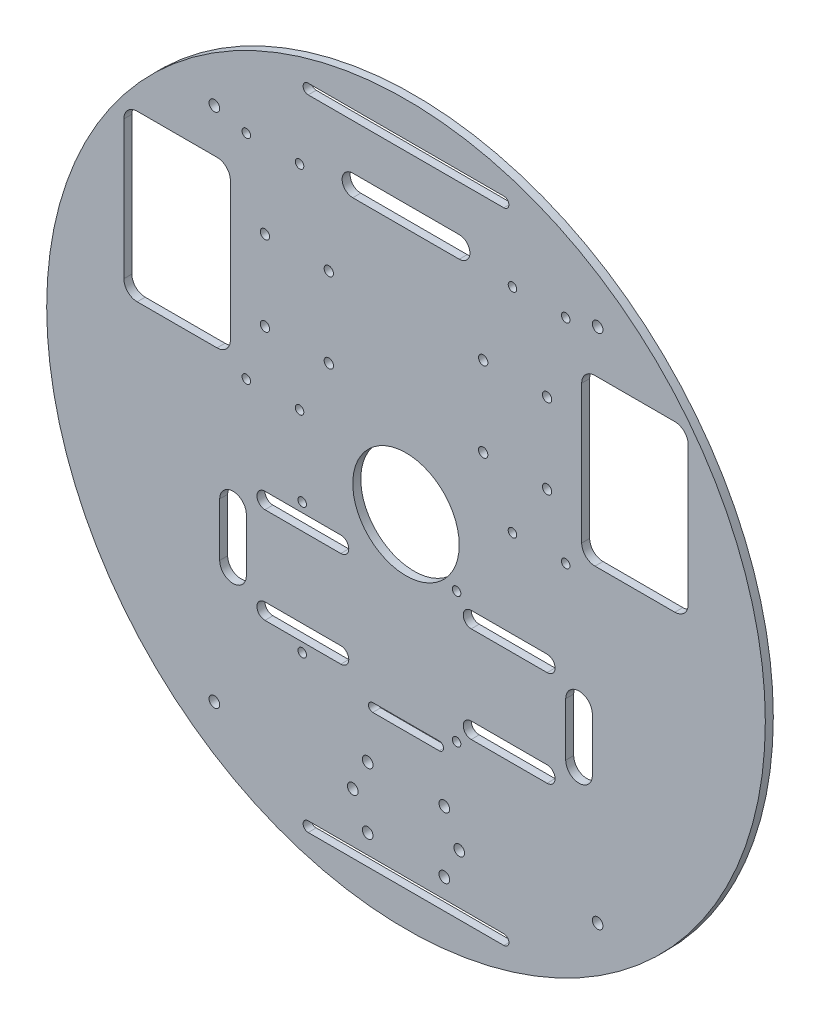
SolidWorks part; units mm, degrees
ref_plane "前视基准面" through (0, 0, 0) normal (0, 0, 1) x (1, 0, 0)
ref_plane "上视基准面" through (0, 0, 0) normal (0, 1, 0) x (1, 0, 0)
ref_plane "右视基准面" through (0, 0, 0) normal (1, 0, 0) x (0, 0, -1)
sketch "草图1" plane through (0, 0, 0) normal (0, 0, 1) x (1, 0, 0)
  line L0 (0, 135) -> (0, -135) construction
  line L1 (0, -99.3042) -> (86, 49.6521) construction
  line L2 (86, 49.6521) -> (-86, 49.6521) construction
  line L3 (-86, 49.6521) -> (0, -99.3042) construction
  line L4 (-106, 80.6521) -> (-66, 80.6521)
  line L5 (-106, 80.6521) -> (-106, 18.6521)
  line L6 (-106, 18.6521) -> (-66, 18.6521)
  line L7 (-66, 80.6521) -> (-66, 18.6521)
  line L8 (-106, 80.6521) -> (-66, 18.6521) construction
  line L9 (-106, 18.6521) -> (-66, 80.6521) construction
  line L10 (106, 80.6521) -> (66, 80.6521)
  line L11 (66, 80.6521) -> (66, 18.6521)
  line L12 (106, 80.6521) -> (66, 18.6521) construction
  line L13 (106, 18.6521) -> (66, 18.6521)
  line L14 (106, 18.6521) -> (66, 80.6521) construction
  line L15 (106, 80.6521) -> (106, 18.6521)
  line L17 (-14.4, -87.8042) -> (14.4, -87.8042) construction
  line L18 (-14.4, -87.8042) -> (-14.4, -110.8042) construction
  line L19 (-14.4, -110.8042) -> (14.4, -110.8042) construction
  line L20 (14.4, -87.8042) -> (14.4, -110.8042) construction
  line L21 (-14.4, -87.8042) -> (14.4, -110.8042) construction
  line L22 (-14.4, -110.8042) -> (14.4, -87.8042) construction
  line L29 (-53, 64.6521) -> (-29, 64.6521) construction
  line L30 (-53, 64.6521) -> (-53, 34.6521) construction
  line L31 (-53, 34.6521) -> (-29, 34.6521) construction
  line L32 (-29, 64.6521) -> (-29, 34.6521) construction
  line L33 (-53, 64.6521) -> (-29, 34.6521) construction
  line L34 (-53, 34.6521) -> (-29, 64.6521) construction
  circle A0 centre (0, 0) radius 135
  circle A1 centre (0, 0) radius 49.6521 construction
  circle A2 centre (-53, 64.6521) radius 1.75
  circle A3 centre (-29, 64.6521) radius 1.75
  circle A4 centre (-53, 34.6521) radius 1.75
  circle A5 centre (-29, 34.6521) radius 1.75
  circle A6 centre (53, 34.6521) radius 1.75
  circle A7 centre (29, 34.6521) radius 1.75
  circle A8 centre (29, 64.6521) radius 1.75
  circle A9 centre (53, 64.6521) radius 1.75
  circle A10 centre (20, -99.3042) radius 2
  circle A11 centre (14.4, -87.8042) radius 2
  circle A12 centre (14.4, -110.8042) radius 2
  circle A13 centre (-14.4, -87.8042) radius 2
  circle A14 centre (-14.4, -110.8042) radius 2
  circle A15 centre (-20, -99.3042) radius 2
  point P25 (0, 49.6521)
  point P26 (-41, 49.6521)
  point P30 (0, 49.6521)
  dimension "D1" = 270
  dimension "D9" = 3.5
  dimension "D10" = 3.5
  dimension "D11" = 3.5
  dimension "D12" = 3.5
  dimension "D14" = 20
  dimension "D2" = 40
  dimension "D3" = 62
  dimension "D4" = 41
  dimension "D5" = 25
  dimension "D6" = 28.8
  dimension "D7" = 24
  dimension "D8" = 30
  dimension "D13" = 23
extrude "凸台-拉伸1" add sketch "草图1" along normal blind 3 contours A0 A14 A9 A7 L10 L15 L13 L11 A2 A3 A4 A5 A6 A8 A10 A11 A12 A13 A15 region at (0, -4.6527, 0)
fillet "圆角1" radius 5 8 edges at (106, 80.6521, 1.5) (66, 80.6521, 1.5) (66, 18.6521, 1.5) (106, 18.6521, 1.5) (-66, 18.6521, 1.5) (-106, 18.6521, 1.5) (-106, 80.6521, 1.5) (-66, 80.6521, 1.5)
sketch "草图2" plane through (0, 0, 3) normal (0, 0, 1) x (1, 0, 0)
  line L1 (-72, 97) -> (72, 97) construction
  line L2 (-72, 97) -> (-72, -97) construction
  line L3 (-72, -97) -> (72, -97) construction
  line L4 (72, 97) -> (72, -97) construction
  line L5 (-72, 97) -> (72, -97) construction
  line L6 (-72, -97) -> (72, 97) construction
  line L7 (24.5056, -55) -> (53, -55)
  line L8 (-53, -19) -> (-24.5056, -19)
  line L9 (-53, -19) -> (-53, -61) construction
  line L10 (-53, -61) -> (-24.5056, -61)
  line L11 (53, -19) -> (53, -61) construction
  line L12 (-53, -19) -> (53, -61) construction
  line L13 (-53, -61) -> (53, -19) construction
  line L14 (-53, -25) -> (-24.5056, -25)
  line L15 (-53, -25) -> (-53, -55) construction
  line L16 (-53, -55) -> (-24.5056, -55)
  line L17 (53, -25) -> (53, -55) construction
  line L18 (-53, -25) -> (53, -55) construction
  line L19 (-53, -55) -> (53, -25) construction
  line L20 (24.5056, -25) -> (53, -25)
  line L21 (24.5056, -19) -> (53, -19)
  line L22 (24.5056, -61) -> (53, -61)
  line L23 (40, 94) -> (40, 14) construction
  line L24 (-65, -30) -> (65, -30) construction
  line L25 (-65, -30) -> (-65, -50) construction
  line L26 (-65, -50) -> (65, -50) construction
  line L27 (65, -30) -> (65, -50) construction
  line L28 (-65, -30) -> (65, -50) construction
  line L29 (-65, -50) -> (65, -30) construction
  line L30 (-70, -30) -> (-60, -30) construction
  line L31 (-70, -30) -> (-70, -50)
  line L32 (-70, -50) -> (-60, -50) construction
  line L33 (-60, -30) -> (-60, -50)
  line L34 (-70, -30) -> (-60, -50) construction
  line L35 (-70, -50) -> (-60, -30) construction
  line L36 (60, -30) -> (70, -30) construction
  line L37 (60, -30) -> (60, -50)
  line L38 (60, -50) -> (70, -50) construction
  line L39 (70, -30) -> (70, -50)
  line L40 (60, -30) -> (70, -50) construction
  line L41 (60, -50) -> (70, -30) construction
  line L43 (35, -12.5) -> (-35, -12.5) construction
  line L44 (35, -12.5) -> (35, -67.5) construction
  line L45 (-42.5, -12) -> (42.5, -12) construction
  line L46 (-42.5, -12) -> (-42.5, -68) construction
  line L47 (-42.5, -68) -> (42.5, -68) construction
  line L48 (-135, 0) -> (135, 0) construction
  line L49 (-36.7556, -118.1) -> (36.7556, -121.9) construction
  line L50 (-36.7556, 121.9) -> (36.7556, 121.9)
  line L51 (-36.7556, 121.9) -> (-36.7556, 118.1) construction
  line L52 (-36.7556, 118.1) -> (36.7556, 118.1)
  line L53 (36.7556, 121.9) -> (36.7556, 118.1) construction
  line L54 (-36.7556, 121.9) -> (36.7556, 118.1) construction
  line L55 (-36.7556, 118.1) -> (36.7556, 121.9) construction
  line L56 (-36.7556, -121.9) -> (36.7556, -118.1) construction
  line L57 (36.7556, -121.9) -> (36.7556, -118.1) construction
  line L58 (-36.7556, -121.9) -> (-36.7556, -118.1) construction
  line L59 (-36.7556, -118.1) -> (36.7556, -118.1)
  line L60 (-36.7556, -121.9) -> (36.7556, -121.9)
  line L61 (-40, 94) -> (-40, 14) construction
  line L62 (-60, 94) -> (60, 94) construction
  line L63 (-60, 94) -> (-60, 14) construction
  line L64 (-60, 14) -> (60, 14) construction
  line L65 (60, 94) -> (60, 14) construction
  line L66 (-60, 94) -> (60, 14) construction
  line L67 (-60, 14) -> (60, 94) construction
  line L68 (42.5, -12) -> (42.5, -68) construction
  line L69 (-42.5, -12) -> (42.5, -68) construction
  line L70 (-42.5, -68) -> (42.5, -12) construction
  line L71 (-39, -15.5) -> (19, -15.5) construction
  line L72 (-39, -15.5) -> (-39, -64.5) construction
  line L73 (-39, -64.5) -> (19, -64.5) construction
  line L74 (19, -15.5) -> (19, -64.5) construction
  line L75 (-39, -15.5) -> (19, -64.5) construction
  line L76 (-39, -64.5) -> (19, -15.5) construction
  line L77 (35, -67.5) -> (-35, -67.5) construction
  line L78 (-35, -12.5) -> (-35, -67.5) construction
  line L79 (35, -12.5) -> (-35, -67.5) construction
  line L80 (35, -67.5) -> (-35, -12.5) construction
  line L81 (12.5, -70.7) -> (-12.5, -70.7)
  line L82 (12.5, -70.7) -> (12.5, -67.5) construction
  line L83 (12.5, -67.5) -> (-12.5, -67.5)
  line L84 (-12.5, -70.7) -> (-12.5, -67.5) construction
  line L85 (12.5, -70.7) -> (-12.5, -67.5) construction
  line L86 (12.5, -67.5) -> (-12.5, -70.7) construction
  line L87 (20, 101) -> (-20, 101)
  line L88 (20, 101) -> (20, 93) construction
  line L89 (20, 93) -> (-20, 93)
  line L90 (-20, 101) -> (-20, 93) construction
  line L91 (20, 101) -> (-20, 93) construction
  line L92 (20, 93) -> (-20, 101) construction
  circle A0 centre (0, 0) radius 20
  circle A1 centre (-72, 97) radius 2
  circle A2 centre (72, 97) radius 2
  circle A3 centre (72, -97) radius 2
  circle A4 centre (-72, -97) radius 2
  arc A5 (-53, -19) -> (-53, -25) centre (-53, -22) ccw
  arc A6 (-53, -55) -> (-53, -61) centre (-53, -58) ccw
  arc A7 (-24.5056, -19) -> (-24.5056, -25) centre (-24.5056, -22) cw
  arc A8 (-24.5056, -61) -> (-24.5056, -55) centre (-24.5056, -58) ccw
  arc A9 (53, -55) -> (53, -61) centre (53, -58) cw
  arc A10 (53, -19) -> (53, -25) centre (53, -22) cw
  arc A11 (24.5056, -61) -> (24.5056, -55) centre (24.5056, -58) cw
  arc A12 (24.5056, -19) -> (24.5056, -25) centre (24.5056, -22) ccw
  arc A13 (-70, -30) -> (-60, -30) centre (-65, -30) cw
  arc A14 (-70, -50) -> (-60, -50) centre (-65, -50) ccw
  arc A15 (60, -30) -> (70, -30) centre (65, -30) cw
  arc A16 (60, -50) -> (70, -50) centre (65, -50) ccw
  circle A17 centre (-60, 94) radius 1.6
  circle A18 centre (-60, 14) radius 1.6
  circle A19 centre (-40, 94) radius 1.6
  circle A20 centre (-40, 14) radius 1.6
  circle A21 centre (60, 14) radius 1.6
  circle A22 centre (60, 94) radius 1.6
  circle A23 centre (40, 94) radius 1.6
  circle A24 centre (40, 14) radius 1.6
  circle A25 centre (0, 0) radius 135 construction
  arc A26 (36.7556, 121.9) -> (36.7556, 118.1) centre (36.7556, 120) cw
  arc A27 (-36.7556, 121.9) -> (-36.7556, 118.1) centre (-36.7556, 120) ccw
  arc A28 (-36.7556, -121.9) -> (-36.7556, -118.1) centre (-36.7556, -120) cw
  arc A29 (36.7556, -121.9) -> (36.7556, -118.1) centre (36.7556, -120) ccw
  circle A30 centre (-39, -15.5) radius 1.6
  circle A31 centre (19, -15.5) radius 1.6
  circle A32 centre (-39, -64.5) radius 1.6
  circle A33 centre (19, -64.5) radius 1.6
  arc A34 (-12.5, -67.5) -> (-12.5, -70.7) centre (-12.5, -69.1) ccw
  arc A35 (12.5, -67.5) -> (12.5, -70.7) centre (12.5, -69.1) cw
  arc A36 (20, 101) -> (20, 93) centre (20, 97) cw
  arc A37 (-20, 101) -> (-20, 93) centre (-20, 97) ccw
  point P25 (0, 54)
  point P32 (0, -40)
  point P37 (-65, -40)
  point P38 (0, -40)
  point P39 (0, -40)
  point P52 (65, -40)
  point P61 (0, -40)
  point P77 (-10, -40)
  point P83 (0, 120)
  point P96 (0, -120)
  point P97 (0, -40)
  point P106 (-42.5, -40)
  point P111 (0, -40)
  point P116 (0, -69.1)
  dimension "D1" = 144
  dimension "D13" = 3.8
  dimension "D15" = 4
  dimension "D16" = 4
  dimension "D17" = 4
  dimension "D18" = 4
  dimension "D12" = 56
  dimension "D26" = 6
  dimension "D27" = 3
  dimension "D28" = 3
  dimension "D2" = 194
  dimension "D3" = 30
  dimension "D4" = 20
  dimension "D5" = 106
  dimension "D6" = 130
  dimension "D7" = 40
  dimension "D8" = 10
  dimension "D9" = 10
  dimension "D10" = 54
  dimension "D14" = 120
  dimension "D19" = 80
  dimension "D20" = 120
  dimension "D21" = 85
  dimension "D22" = 3.5
  dimension "D23" = 58
  dimension "D24" = 49
  dimension "D25" = 3.5
  dimension "D29" = 70
  dimension "D30" = 55
  dimension "D31" = 25
  dimension "D32" = 3.2
  dimension "D33" = 8
  dimension "D34" = 40
extrude "切除-拉伸1" cut sketch "草图2" against normal blind 10
sketch "草图3" plane through (0, 0, 3) normal (0, 0, 1) x (1, 0, 0)
  line L0 (0, 0) -> (0, -135) construction
  line L1 (0, 93) -> (0, 0) construction
  line L2 (35, -8.8786) -> (-35, -8.8786) construction
  line L3 (35, -8.8786) -> (35, -63.8786) construction
  line L4 (35, -63.8786) -> (-35, -63.8786) construction
  line L5 (-35, -8.8786) -> (-35, -63.8786) construction
  line L6 (35, -8.8786) -> (-35, -63.8786) construction
  line L7 (35, -63.8786) -> (-35, -8.8786) construction
  line L8 (-20, 93) -> (20, 93) construction
  circle A0 centre (0, 0) radius 135 construction
  point P6 (0, -36.3786)
  dimension "D1" = 55
  dimension "D2" = 70
  dimension "D3" = 93
